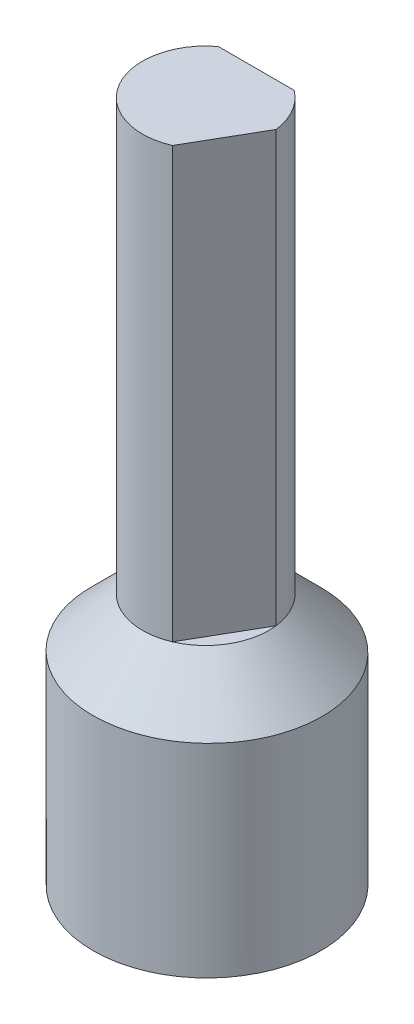
SolidWorks part; units mm, degrees
ref_plane "Front Plane" through (0, 0, 0) normal (0, 0, 1) x (1, 0, 0)
ref_plane "Top Plane" through (0, 0, 0) normal (0, 1, 0) x (1, 0, 0)
ref_plane "Right Plane" through (0, 0, 0) normal (1, 0, 0) x (0, 0, -1)
sketch "Sketch1" plane through (0, 0, 0) normal (0, 1, 0) x (1, 0, 0)
  line L0 (4.55, 9.1) -> (4.55, 0) construction
  line L1 (0, 0) -> (9.1, 0)
  line L2 (0, 0) -> (0, 9.1)
  line L3 (0, 9.1) -> (9.1, 9.1)
  line L4 (9.1, 0) -> (9.1, 9.1)
  circle A0 centre (4.55, 4.55) radius 9
  dimension "D2" = 18
  dimension "D1" = 9.1
extrude "Boss-Extrude1" add sketch "Sketch1" along normal blind 13 contours A0 | L2 L1 L4 L3
sketch "Sketch2" plane through (0, 13, 0) normal (0, 1, 0) x (1, 0, 0)
  line L0 (4.55, 13.55) -> (4.55, -4.45) construction
  circle A0 centre (4.55, 4.55) radius 9 construction
  circle A1 centre (4.55, 4.55) radius 9
  dimension "D1" = 18
extrude "Boss-Extrude2" add sketch "Sketch2" along normal blind 1
sketch "Sketch3" plane through (0, 14, 0) normal (0, 1, 0) x (1, 0, 0)
  line L0 (4.55, 13.55) -> (4.55, -4.45) construction
  circle A0 centre (4.55, 4.55) radius 9 construction
  circle A1 centre (4.55, 4.4431) radius 5
  dimension "D1" = 10
extrude "Boss-Extrude3" add sketch "Sketch3" along normal blind 40
chamfer "Chamfer1" distance 6 1 edges at (4.55, 14, 0.5569)
sketch "Sketch4" plane through (0, 54, 0) normal (0, 1, 0) x (1, 0, 0)
  line L0 (13.2903, 2.861) -> (9.5141, 5.0412)
  line L1 (1.55, 12.8035) -> (7.55, 12.8035)
  line L2 (1.55, 12.8035) -> (1.55, 8.4431)
  line L3 (1.55, 8.4431) -> (7.55, 8.4431)
  line L4 (7.55, 12.8035) -> (7.55, 8.4431)
  line L5 (13.2903, 2.861) -> (10.2903, -2.3352)
  line L6 (10.2903, -2.3352) -> (6.5141, -0.155)
  line L7 (9.5141, 5.0412) -> (6.5141, -0.155)
  circle A0 centre (4.55, 4.4431) radius 5 construction
  circle A1 centre (4.55, 4.4431) radius 5 construction
  circle A2 centre (4.55, 4.4431) radius 5 construction
  point P18 (4.55, 4.4431)
  dimension "D1" = 4
  dimension "D2" = 2
extrude "Cut-Extrude1" cut sketch "Sketch4" against normal blind 34
